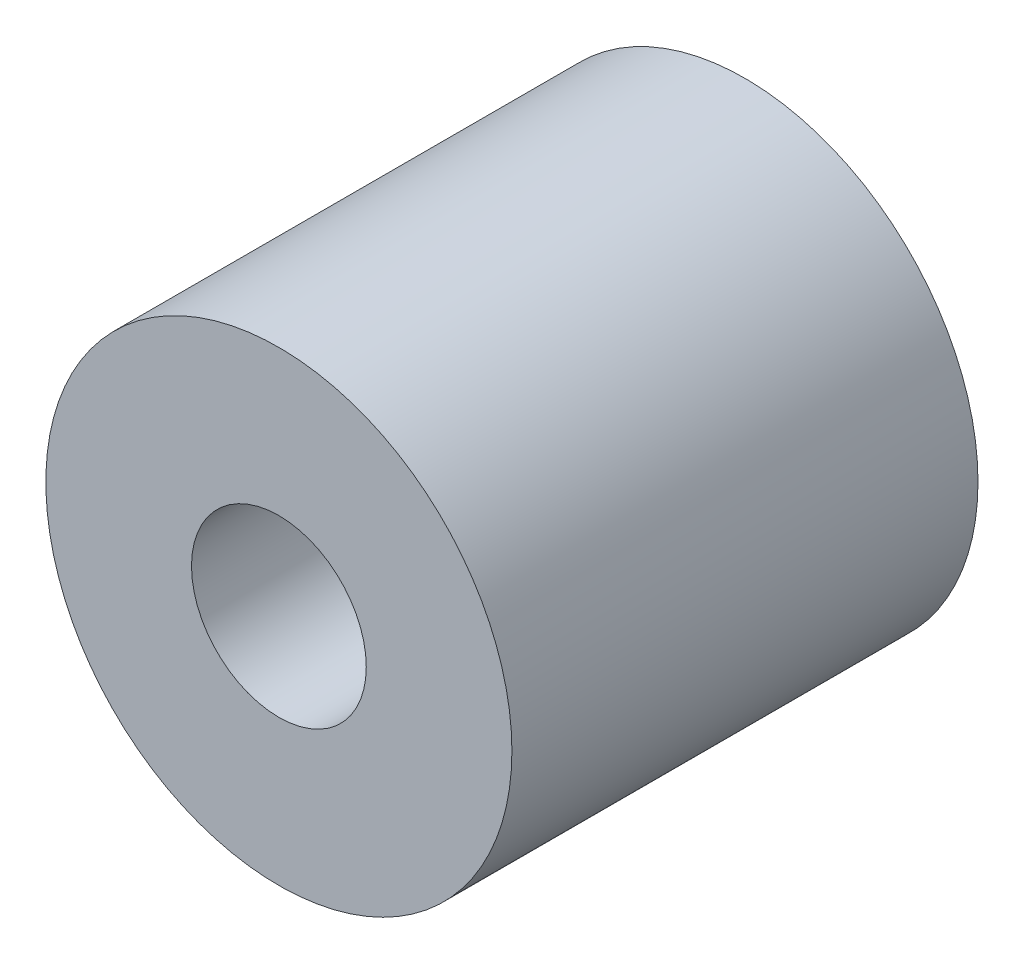
SolidWorks part; units mm, degrees
ref_plane "Front Plane" through (0, 0, 0) normal (0, 0, 1) x (1, 0, 0)
ref_plane "Top Plane" through (0, 0, 0) normal (0, 1, 0) x (1, 0, 0)
ref_plane "Right Plane" through (0, 0, 0) normal (1, 0, 0) x (0, 0, -1)
sketch "Sketch1" plane through (0, 0, 0) normal (0, 0, 1) x (1, 0, 0)
  circle A0 centre (0, 0) radius 4
  circle A1 centre (0, 0) radius 3.075
  dimension "D1" = 8
  dimension "D2" = 6.15
extrude "Boss-Extrude1" add sketch "Sketch1" along normal blind 8
sketch "Sketch2" plane through (0, 0, 8) normal (0, 0, 1) x (1, 0, 0)
  circle A0 centre (0, 0) radius 3.075
  circle A1 centre (0, 0) radius 1.5
  dimension "D1" = 3
  dimension "D2" = 6.15
extrude "Boss-Extrude2" add sketch "Sketch2" against normal offset from surface (5.5 mm away) 2.5 up to face at (4, 0, 0)
